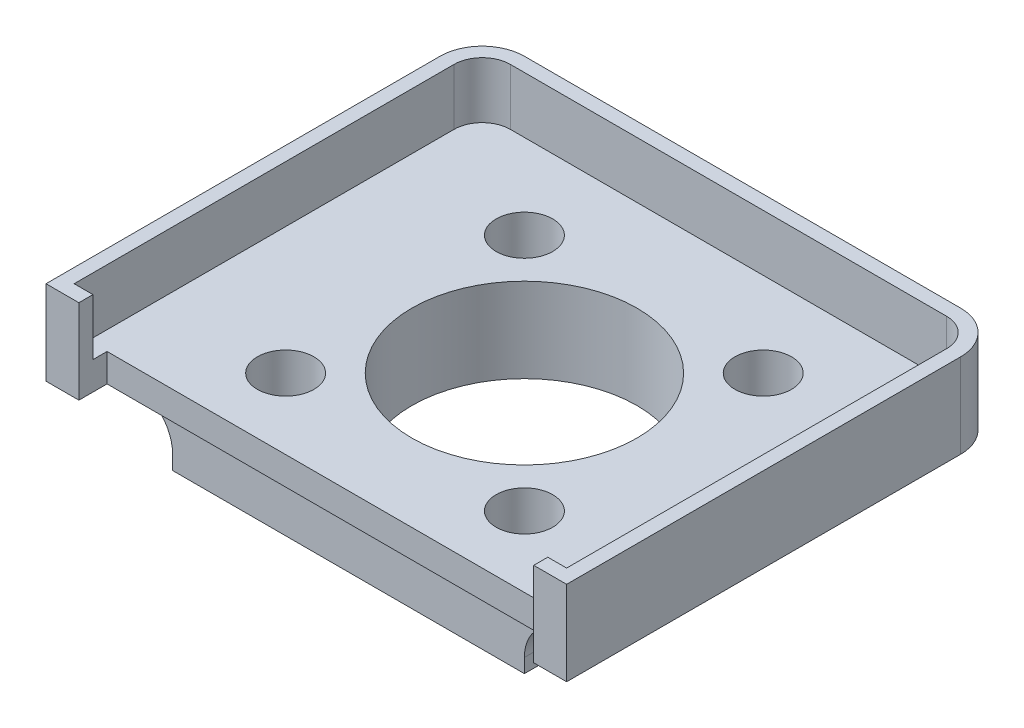
SolidWorks part; units mm, degrees
ref_plane "前视基准面" through (0, 0, 0) normal (0, 0, 1) x (1, 0, 0)
ref_plane "上视基准面" through (0, 0, 0) normal (0, 1, 0) x (1, 0, 0)
ref_plane "右视基准面" through (0, 0, 0) normal (1, 0, 0) x (0, 0, -1)
sketch "草图1" plane through (0, 0, 0) normal (0, 1, 0) x (1, 0, 0)
  line L1 (17.5, -14.5) -> (-17.5, -14.5)
  line L2 (17.5, -14.5) -> (17.5, 14.5)
  line L3 (17.5, 14.5) -> (-17.5, 14.5)
  line L4 (-17.5, -14.5) -> (-17.5, 14.5)
  line L5 (17.5, -14.5) -> (-17.5, 14.5) construction
  line L6 (17.5, 14.5) -> (-17.5, -14.5) construction
  point P0 (0, 0)
  point P5 (-3.4363, 2.4569)
extrude "拉伸-薄壁1" add sketch "草图1" along normal blind 6 thin contours L4 L3 L2 L1 thin type one direction wall 1
sketch "草图2" plane through (0, 0, 0) normal (0, -1, 0) x (1, 0, 0)
  line L1 (18.5, 15.5) -> (-18.5, 15.5)
  line L2 (18.5, 15.5) -> (18.5, -15.5)
  line L3 (18.5, -15.5) -> (-18.5, -15.5)
  line L4 (-18.5, 15.5) -> (-18.5, -15.5)
  point P4 (0, 0)
  point P6 (0, 0)
extrude "凸台-拉伸1" add sketch "草图2" against normal blind 2
sketch "草图3" plane through (0, 0, 15.5) normal (0, 0, 1) x (1, 0, 0)
  line L1 (-16.1622, 0) -> (16.1622, 0)
  line L2 (-16.1622, 0) -> (-16.1622, 15.9889)
  line L3 (-16.1622, 15.9889) -> (16.1622, 15.9889)
  line L4 (16.1622, 0) -> (16.1622, 15.9889)
  line L5 (-16.1622, 0) -> (16.1622, 15.9889) construction
  line L6 (-16.1622, 15.9889) -> (16.1622, 0) construction
  line L7 (18.5, 0) -> (-18.5, 0) construction
  point P0 (0, 7.9945)
  point P5 (0, 0)
  point P6 (0, 0)
  point P7 (0, 0)
extrude "切除-拉伸1" cut sketch "草图3" against normal blind 2 contours L3 L4 L1 L2
sketch "草图4" plane through (0, 0, 0) normal (0, -1, 0) x (-1, 0, 0)
  line L1 (12.5, 12.5) -> (-12.5, 12.5)
  line L2 (12.5, 12.5) -> (12.5, -12.5)
  line L3 (12.5, -12.5) -> (-12.5, -12.5)
  line L4 (-12.5, 12.5) -> (-12.5, -12.5)
  line L5 (12.5, 12.5) -> (-12.5, -12.5) construction
  line L6 (12.5, -12.5) -> (-12.5, 12.5) construction
  point P0 (0, 0)
extrude "凸台-拉伸2" add sketch "草图4" along normal blind 4
sketch "草图5" plane through (0, -4, 0) normal (0, -1, 0) x (-1, 0, 0)
  line L0 (0, 0) -> (8.4853, 8.4853) construction
  circle A0 centre (8.4853, 8.4853) radius 2.01
  circle A1 centre (8.4853, -8.4853) radius 2.01
  circle A2 centre (-8.4853, -8.4853) radius 2.01
  circle A3 centre (-8.4853, 8.4853) radius 2.01
  circle A4 centre (0, 0) radius 8
  point P6 (0, 0)
  point P12 (0, 0)
  dimension "D1" = 4
extrude "切除-拉伸2" cut sketch "草图5" against normal blind 13
fillet "圆角1" radius 3 1 edges at (12.5, 0, 0)
fillet "圆角2" radius 3 1 edges at (-12.5, 0, 0)
fillet "圆角3" radius 3 3 edges at (13.3787, -0.8787, -12.5) (-13.3787, -0.8787, -12.5) (0, 0, -12.5)
fillet "圆角4" radius 3 2 edges at (13.3787, -0.8787, -13.3787) (12.5, -3.5, -12.5)
fillet "圆角5" radius 3 2 edges at (-13.3787, -0.8787, -13.3787) (-12.5, -3.5, -12.5)
fillet "圆角6" radius 3 2 edges at (-17, 0, -15.5) (-18.5, 3, -15.5)
fillet "圆角7" radius 3 2 edges at (17, 0, -15.5) (18.5, 3, -15.5)
fillet "圆角12" radius 2 1 edges at (-17.5, 4, -14.5)
fillet "圆角13" radius 2 1 edges at (17.5, 4, -14.5)
